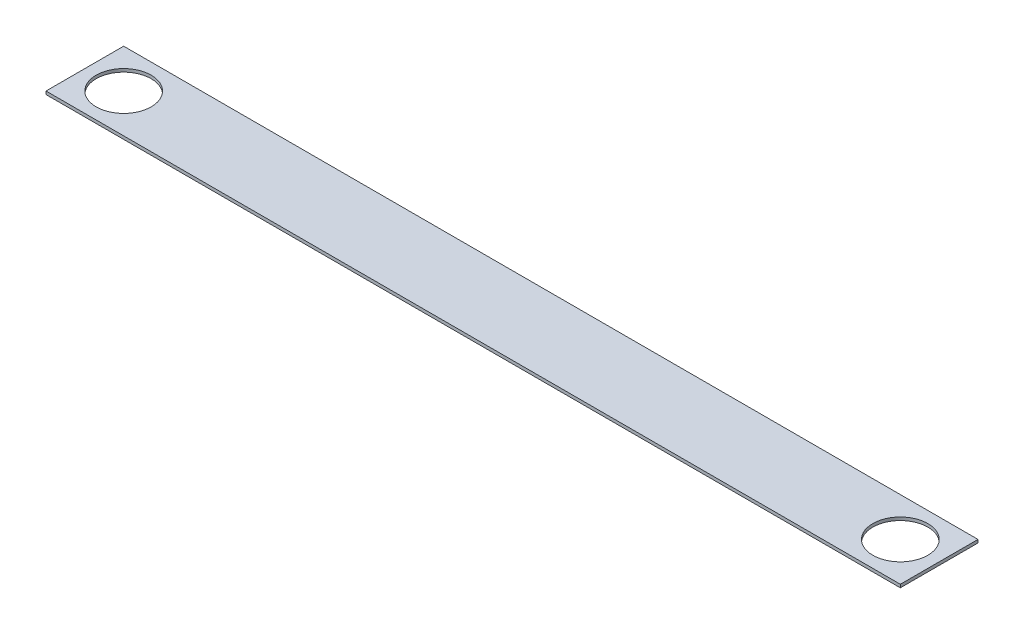
SolidWorks part; units mm, degrees
material "Cast Alloy Steel"
ref_plane "Front Plane" through (0, 0, 0) normal (0, 0, 1) x (1, 0, 0)
ref_plane "Top Plane" through (0, 0, 0) normal (0, 1, 0) x (1, 0, 0)
ref_plane "Right Plane" through (0, 0, 0) normal (1, 0, 0) x (0, 0, -1)
sketch "Sketch1" plane through (0, 0, 0) normal (0, 1, 0) x (1, 0, 0)
  line L1 (-34.925, -3.175) -> (34.925, -3.175)
  line L2 (-34.925, -3.175) -> (-34.925, 3.175)
  line L3 (-34.925, 3.175) -> (34.925, 3.175)
  line L4 (34.925, -3.175) -> (34.925, 3.175)
  line L5 (-34.925, -3.175) -> (34.925, 3.175) construction
  line L6 (-34.925, 3.175) -> (34.925, -3.175) construction
  point P0 (0, 0)
  dimension "D1" = 69.85
  dimension "D2" = 6.35
extrude "Boss-Extrude1" add sketch "Sketch1" along normal blind 0.254
hole_wizard "#8 Clearance Hole1" positions "Sketch2" profile "Sketch3" hole size "#8" standard "ANSI Inch" end condition up to next
sketch "Sketch2" plane through (0, 0.254, 0) normal (0, 1, 0) x (1, 0, 0)
  line L0 (-34.925, 3.175) -> (-34.925, -3.175) construction
  line L1 (34.925, -3.175) -> (34.925, 3.175) construction
  point P0 (-31.75, 0)
  point P2 (31.75, 0)
  dimension "D1" = 3.175
  dimension "D2" = 3.175
sketch "Sketch3" plane through (-31.75, 0.254, 0) normal (1, 0, 0) x (0, 0, 1)
  line L0 (0, 0) -> (0, 0.254)
  line L1 (0, 0.254) -> (2.2479, 0.254)
  line L2 (2.2479, 0.254) -> (2.2479, 0)
  line L5 (2.2479, 0) -> (0, 0)
  line L11 (0, -6.35) -> (0, 107.95) construction
  dimension "Thru Hole Dia." = 4.4958
  dimension "Thru Hole Depth" = 0.254
